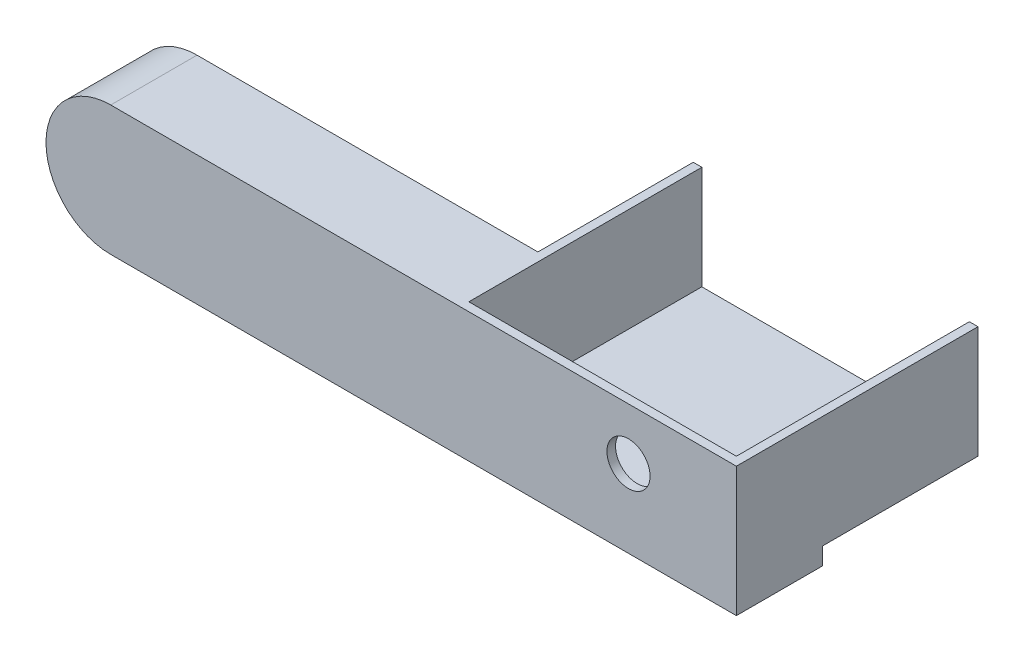
SolidWorks part; units mm, degrees
ref_plane "Front Plane" through (0, 0, 0) normal (0, 0, 1) x (1, 0, 0)
ref_plane "Top Plane" through (0, 0, 0) normal (0, 1, 0) x (1, 0, 0)
ref_plane "Right Plane" through (0, 0, 0) normal (1, 0, 0) x (0, 0, -1)
other "Configuration Table"
sketch "Sketch1" plane through (0, 0, 0) normal (0, 0, 1) x (1, 0, 0)
  line L5 (0, 0) -> (80, 0)
  line L6 (0, 0) -> (0, 15)
  line L7 (0, 15) -> (80, 15)
  line L8 (80, 0) -> (80, 15)
  dimension "D1" = 80
  dimension "D2" = 15
extrude "Boss-Extrude1" add sketch "Sketch1" along normal blind 10
fillet "Fillet1" radius 7.5 2 edges at (0, 0, 5) (0, 15, 5)
sketch "Sketch2" plane through (0, 0, 10) normal (0, 0, 1) x (1, 0, 0)
  circle A0 centre (7.5, 7.5) radius 2.5
  circle A1 centre (7.5, 7.5) radius 3.5
  circle A2 centre (72.5, 7.5) radius 2.5
  circle A3 centre (72.5, 7.5) radius 3.5
  dimension "D1" = 5
  dimension "D2" = 5
  dimension "D3" = 7
  dimension "D4" = 7
extrude "Boss-Extrude2" add sketch "Sketch2" along normal blind 2 and the other way blind 13
sketch "Sketch4" plane through (80, 0, 0) normal (1, 0, 0) x (0, 0, -1)
  line L5 (0, 15) -> (12.2756, 15)
  line L6 (0, 15) -> (0, 0)
  line L7 (0, 0) -> (12.2756, 0)
  line L8 (12.2756, 15) -> (12.2756, 0)
extrude "Cut-Extrude1" cut sketch "Sketch4" against normal blind 39
ref_plane "Plane1" through (0, 7.5, 0) normal (0, 0, -1) x (-1, 0, 0)
sketch "Sketch6" plane through (0, 0, 0) normal (1, 0, 0) x (0, 0, -1)
  line L0 (-10, 7.5) -> (-10, 0) construction
  line L1 (-10, 14.8873) -> (-20, 14.8873)
  line L2 (-10, 14.8873) -> (-10, 0)
  line L3 (-10, 0) -> (-20, 0)
  line L4 (-20, 14.8873) -> (-20, 0)
  dimension "D1" = 10
  dimension "D2" = 10
  dimension "D3" = 0
extrude "Cut-Extrude2" cut sketch "Sketch6" along normal blind 39
sketch "Sketch8" plane through (0, 15, 0) normal (0, 1, 0) x (1, 0, 0)
  line L5 (47, 18) -> (80, 18)
  line L6 (47, 18) -> (47, -10)
  line L7 (47, -10) -> (80, -10)
  line L8 (80, 18) -> (80, -10)
  dimension "D3" = 33
  dimension "D4" = 28
extrude "Boss-Extrude3" add sketch "Sketch8" against normal blind 15
sketch "Sketch9" plane through (0, 15, 0) normal (0, 1, 0) x (1, 0, 0)
  line L0 (80, 18) -> (47, 18) construction
  line L2 (48, 17) -> (48, -9)
  line L3 (48, -9) -> (79, -9)
  line L4 (79, 17) -> (79, -9)
  line L5 (80, -10) -> (7.5, -10) construction
  line L6 (80, -10) -> (80, 18) construction
  line L7 (47, 18) -> (47, 0) construction
  line L8 (48, 17) -> (48, 18)
  line L9 (79, 17) -> (79, 18)
  line L11 (48, 18) -> (79, 18)
  dimension "D2" = 1
  dimension "D3" = 1
  dimension "D4" = 1
extrude "Cut-Extrude3" cut sketch "Sketch9" against normal blind 12
sketch "Sketch10" plane through (0, 0, 0) normal (0, -1, 0) x (1, 0, 0)
  line L8 (47, 0) -> (80, 0)
  line L13 (47, 0) -> (47, -18)
  line L14 (47, -18) -> (80, -18)
  line L15 (80, 0) -> (80, -18)
extrude "Cut-Extrude4" cut sketch "Sketch10" against normal blind 2
sketch "Sketch11" plane through (80, 0, 0) normal (1, 0, 0) x (0, 0, -1)
  line L1 (-10, 15) -> (-21.4387, 15)
  line L2 (-10, 15) -> (-10, 0)
  line L3 (-10, 0) -> (-21.4387, 0)
  line L4 (-21.4387, 15) -> (-21.4387, 0)
extrude "Cut-Extrude5" cut sketch "Sketch11" against normal through all
sketch "Sketch12" plane through (0, 0, 9) normal (0, 0, -1) x (-1, 0, 0)
  line L0 (-79, 3) -> (-79, 15) construction
  circle A0 centre (-67.5, 9) radius 2.5
  dimension "D1" = 5
  dimension "D2" = 11.5
extrude "Cut-Extrude6" cut sketch "Sketch12" against normal through all
